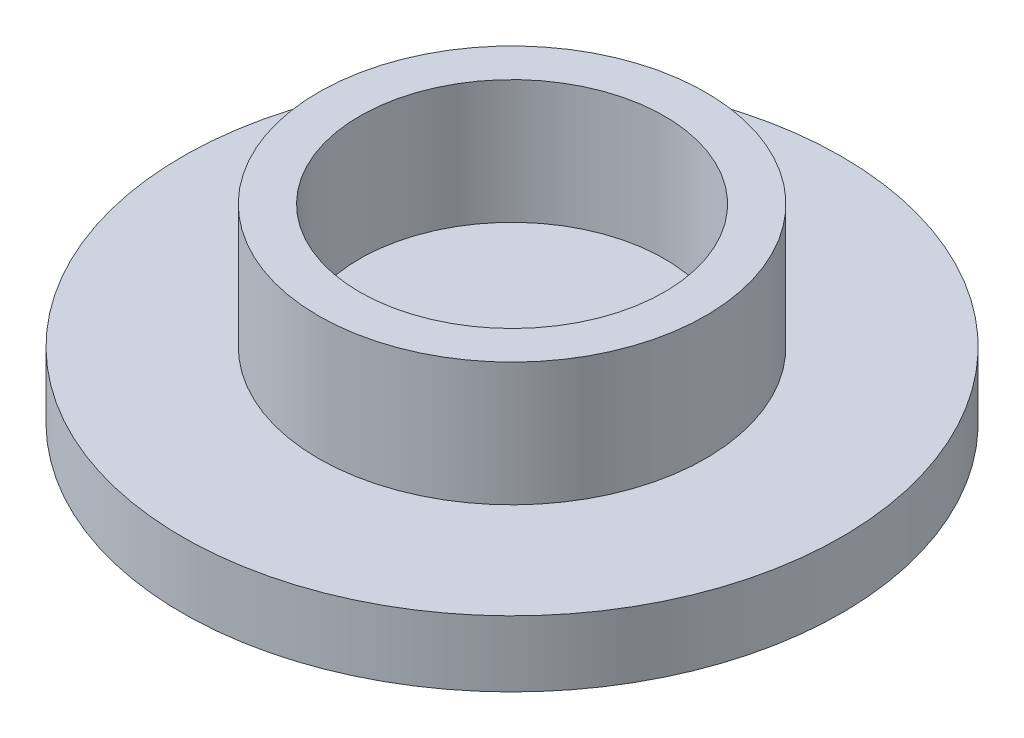
SolidWorks part; units mm, degrees
ref_plane "Front Plane" through (0, 0, 0) normal (0, 0, 1) x (1, 0, 0)
ref_plane "Top Plane" through (0, 0, 0) normal (0, 1, 0) x (1, 0, 0)
ref_plane "Right Plane" through (0, 0, 0) normal (1, 0, 0) x (0, 0, -1)
sketch "Sketch1" plane through (0, 0, 0) normal (0, 1, 0) x (1, 0, 0)
  circle A0 centre (0, 0) radius 1.85
  circle A1 centre (0, 0) radius 2.35
  dimension "D1" = 3.7
  dimension "D2" = 4.7
extrude "Boss-Extrude1" add sketch "Sketch1" along normal blind 1.5
sketch "Sketch2" plane through (0, 0, 0) normal (0, -1, 0) x (1, 0, 0)
  circle A0 centre (0, 0) radius 4
  dimension "D1" = 8
extrude "Boss-Extrude2" add sketch "Sketch2" along normal blind 0.8
